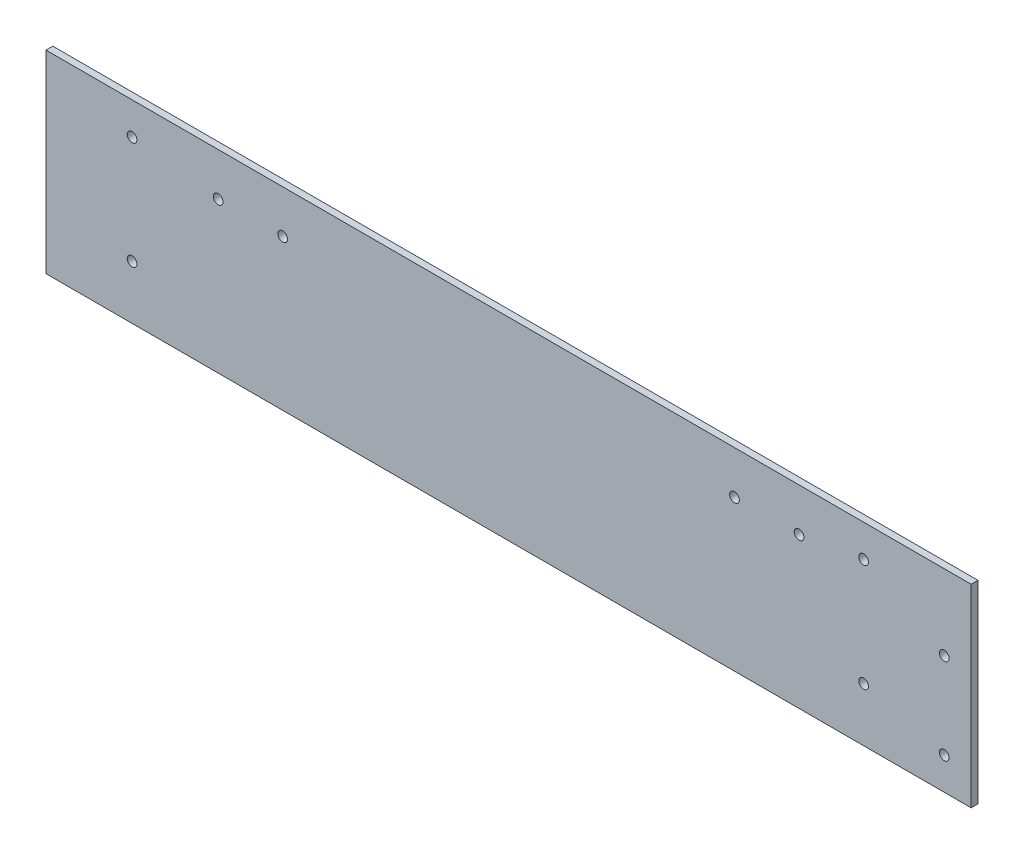
SolidWorks part; units mm, degrees
ref_plane "Front Plane" through (0, 0, 0) normal (0, 0, 1) x (1, 0, 0)
ref_plane "Top Plane" through (0, 0, 0) normal (0, 1, 0) x (1, 0, 0)
ref_plane "Right Plane" through (0, 0, 0) normal (1, 0, 0) x (0, 0, -1)
sketch "Sketch1" plane through (0, 0, 0) normal (0, 0, 1) x (1, 0, 0)
  line L1 (-215, -45) -> (215, -45)
  line L2 (-215, -45) -> (-215, 45)
  line L3 (-215, 45) -> (215, 45)
  line L4 (215, -45) -> (215, 45)
  line L5 (-215, -45) -> (215, 45) construction
  line L6 (-215, 45) -> (215, -45) construction
  point P0 (0, 0)
  dimension "D1" = 430
  dimension "D2" = 90
extrude "Boss-Extrude1" add sketch "Sketch1" along normal blind 3.175
hole_wizard "M4 Clearance Hole1" positions "Sketch2" profile "Sketch3" hole size "M4" standard "ANSI Metric" end condition through all
sketch "Sketch2" plane through (0, 0, 3.175) normal (0, 0, 1) x (1, 0, 0)
  line L1 (-175, -20) -> (165, -20)
  line L2 (-175, -20) -> (-175, 30)
  line L3 (-175, 30) -> (165, 30)
  line L4 (165, -20) -> (165, 30)
  line L5 (-175, -20) -> (165, 30) construction
  line L6 (-175, 30) -> (165, -20) construction
  line L7 (-215, 45) -> (-215, -45) construction
  line L8 (215, -45) -> (215, 45) construction
  line L9 (-215, -45) -> (215, -45) construction
  point P2 (165, 30)
  point P59 (-175, -20)
  point P60 (-175, 30)
  point P61 (165, -20)
  dimension "D1" = 50
  dimension "D2" = 40
  dimension "D3" = 50
  dimension "D4" = 25
sketch "Sketch3" plane through (165, 30, 3.175) normal (1, 0, 0) x (0, -1, 0)
  line L0 (0, 0) -> (0, 3.175)
  line L1 (0, 3.175) -> (2.25, 3.175)
  line L2 (2.25, 3.175) -> (2.25, 0)
  line L5 (2.25, 0) -> (0, 0)
  line L11 (0, -6.35) -> (0, 107.95) construction
  dimension "Thru Hole Dia." = 4.5
  dimension "Thru Hole Depth" = 3.175
hole_wizard "M4 Clearance Hole2" positions "Sketch4" profile "Sketch5" hole size "M4" standard "ANSI Metric" end condition through all
sketch "Sketch4" plane through (0, 0, 3.175) normal (0, 0, 1) x (1, 0, 0)
  line L0 (-135, 25) -> (-105, 25)
  line L1 (215, 45) -> (-215, 45) construction
  line L2 (-215, 45) -> (-215, -45) construction
  point P1 (-135, 25)
  point P2 (-105, 25)
  dimension "D1" = 30
  dimension "D2" = 20
  dimension "D3" = 80
sketch "Sketch5" plane through (-135, 25, 3.175) normal (1, 0, 0) x (0, -1, 0)
  line L0 (0, 0) -> (0, 3.175)
  line L1 (0, 3.175) -> (2.25, 3.175)
  line L2 (2.25, 3.175) -> (2.25, 0)
  line L5 (2.25, 0) -> (0, 0)
  line L11 (0, -6.35) -> (0, 107.95) construction
  dimension "Thru Hole Dia." = 4.5
  dimension "Thru Hole Depth" = 3.175
mirror "Mirror1" about plane through (0, 0, 0) normal (1, 0, 0) of "M4 Clearance Hole2"
hole_wizard "M4 Clearance Hole3" positions "Sketch6" profile "Sketch7" hole size "M4" standard "ANSI Metric" end condition through all
sketch "Sketch6" plane through (0, 0, 3.175) normal (0, 0, 1) x (1, 0, 0)
  line L0 (202.5, -30) -> (202.5, 10)
  line L2 (215, -45) -> (215, 45) construction
  point P1 (202.5, -30)
  point P2 (202.5, 10)
  dimension "D1" = 15
  dimension "D2" = 12.5
  dimension "D3" = 40
sketch "Sketch7" plane through (202.5, -30, 3.175) normal (1, 0, 0) x (0, -1, 0)
  line L0 (0, 0) -> (0, 3.175)
  line L1 (0, 3.175) -> (2.25, 3.175)
  line L2 (2.25, 3.175) -> (2.25, 0)
  line L5 (2.25, 0) -> (0, 0)
  line L11 (0, -6.35) -> (0, 107.95) construction
  dimension "Thru Hole Dia." = 4.5
  dimension "Thru Hole Depth" = 3.175
